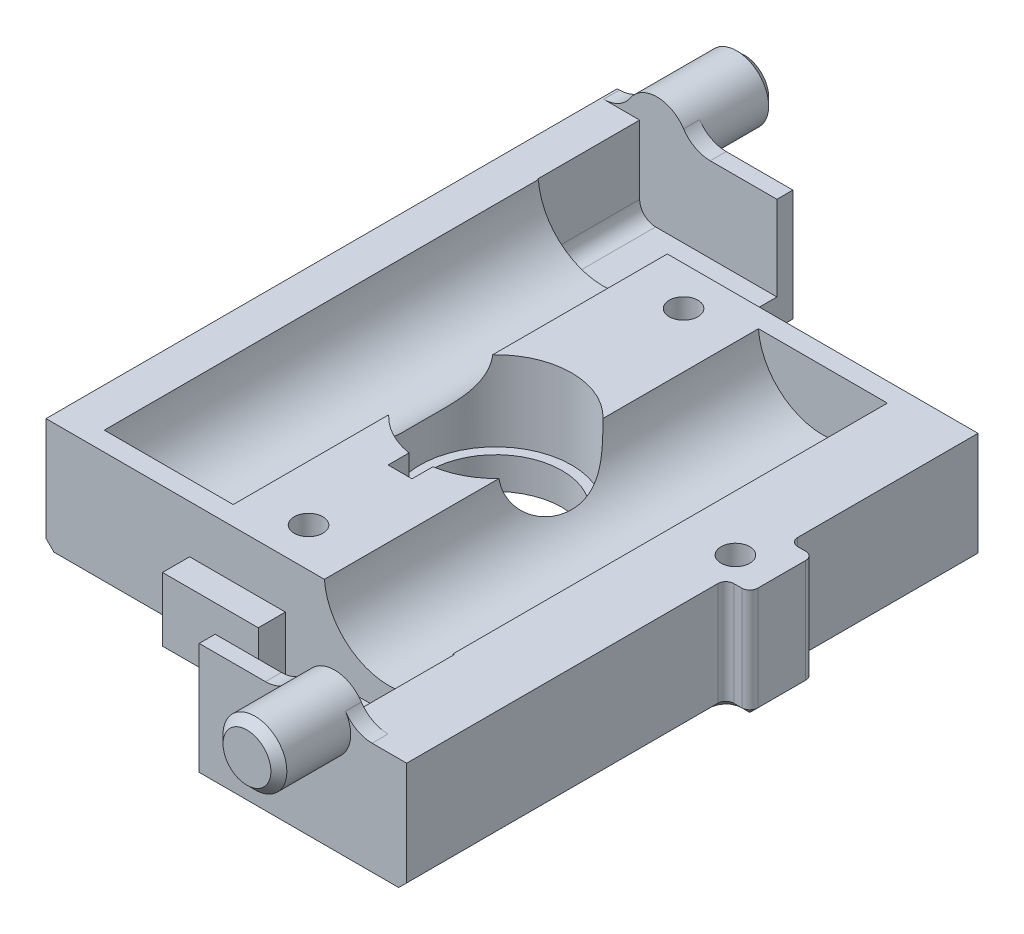
SolidWorks part; units mm, degrees
ref_plane "Front Plane" through (0, 0, 0) normal (0, 0, 1) x (1, 0, 0)
ref_plane "Top Plane" through (0, 0, 0) normal (0, 1, 0) x (1, 0, 0)
ref_plane "Right Plane" through (0, 0, 0) normal (1, 0, 0) x (0, 0, -1)
sketch "Sketch1" plane through (0, 0, 0) normal (0, 1, 0) x (1, 0, 0)
  line L1 (-61.4569, -66.3705) -> (-31.4569, -66.3705)
  line L2 (-61.4569, -66.3705) -> (-61.4569, -35.5705)
  line L3 (-61.4569, -35.5705) -> (-31.4569, -35.5705)
  line L4 (-31.4569, -66.3705) -> (-31.4569, -35.5705)
  dimension "D1" = 30.8
  dimension "D2" = 30
extrude "Boss-Extrude1" add sketch "Sketch1" along normal blind 7
sketch "Sketch2" plane through (0, 0, 0) normal (0, -1, 0) x (1, 0, 0)
  circle A0 centre (-47.4719, 50.9705) radius 4.15
  dimension "D1" = 8.3
extrude "Cut-Extrude1" cut sketch "Sketch2" against normal blind 6.5
sketch "Sketch3" plane through (0, 0, 0) normal (0, -1, 0) x (1, 0, 0)
  line L1 (-31.4569, 66.3705) -> (-46.4569, 66.3705)
  line L2 (-31.4569, 66.3705) -> (-31.4569, 65.1705)
  line L3 (-31.4569, 65.1705) -> (-46.4569, 65.1705)
  line L4 (-46.4569, 66.3705) -> (-46.4569, 65.1705)
  line L5 (-61.4569, 66.3705) -> (-52.4569, 66.3705)
  line L6 (-61.4569, 66.3705) -> (-61.4569, 65.1705)
  line L7 (-61.4569, 65.1705) -> (-52.4569, 65.1705)
  line L8 (-52.4569, 66.3705) -> (-52.4569, 65.1705)
  line L9 (-31.4569, 35.5705) -> (-42.4569, 35.5705)
  line L10 (-31.4569, 35.5705) -> (-31.4569, 36.7705)
  line L11 (-31.4569, 36.7705) -> (-42.4569, 36.7705)
  line L12 (-42.4569, 35.5705) -> (-42.4569, 36.7705)
  line L13 (-61.4569, 35.5705) -> (-48.4569, 35.5705)
  line L14 (-61.4569, 35.5705) -> (-61.4569, 36.7705)
  line L15 (-61.4569, 36.7705) -> (-48.4569, 36.7705)
  line L16 (-48.4569, 35.5705) -> (-48.4569, 36.7705)
  dimension "D1" = 15
  dimension "D2" = 9
  dimension "D3" = 1.2
  dimension "D4" = 1.2
  dimension "D5" = 1.2
  dimension "D6" = 1.2
  dimension "D7" = 11
  dimension "D8" = 13
extrude "Cut-Extrude2" cut sketch "Sketch3" against normal blind 4
sketch "Sketch4" plane through (0, 0, 66.3705) normal (0, 0, 1) x (1, 0, 0)
  line L1 (-61.4569, 7) -> (-31.4569, 7)
  line L2 (-61.4569, 7) -> (-61.4569, 4)
  line L3 (-61.4569, 4) -> (-31.4569, 4)
  line L4 (-31.4569, 7) -> (-31.4569, 4)
extrude "Cut-Extrude3" cut sketch "Sketch4" against normal blind 1.2
sketch "Sketch5" plane through (0, 0, 35.5705) normal (0, 0, -1) x (-1, 0, 0)
  line L1 (61.4569, 4) -> (31.4569, 4)
  line L2 (61.4569, 4) -> (61.4569, 7)
  line L3 (61.4569, 7) -> (31.4569, 7)
  line L4 (31.4569, 4) -> (31.4569, 7)
extrude "Cut-Extrude4" cut sketch "Sketch5" against normal blind 1.2
sketch "Sketch6" plane through (0, 0, 65.1705) normal (0, 0, 1) x (1, 0, 0)
  line L0 (-44.0746, 7.3) -> (-35.8746, 7.3) construction
  circle A0 centre (-39.9746, 7.3) radius 4.05
  dimension "D1" = 8.1
extrude "Cut-Extrude5" cut sketch "Sketch6" against normal blind 27.2
sketch "Sketch7" plane through (0, 0, 36.7705) normal (0, 0, -1) x (-1, 0, 0)
  line L0 (50.8646, 7.3) -> (59.0646, 7.3) construction
  circle A0 centre (54.9646, 7.3) radius 4.05
  dimension "D1" = 8.1
extrude "Cut-Extrude6" cut sketch "Sketch7" against normal blind 27.2
sketch "Sketch8" plane through (0, 7, 0) normal (0, 1, 0) x (1, 0, 0)
  circle A0 centre (-47.4719, -50.9705) radius 4.75
  dimension "D1" = 9.5
extrude "Cut-Extrude7" cut sketch "Sketch8" against normal blind 5
sketch "Sketch10" plane through (0, 0, 65.1705) normal (0, 0, 1) x (1, 0, 0)
  line L5 (-31.4569, 0) -> (-31.4569, 7)
  line L6 (-31.4569, 7) -> (-35.8569, 7)
  line L7 (-31.4569, 7) -> (-35.9357, 7) construction
  line L8 (-35.8569, 7) -> (-35.8569, 1.7)
  line L9 (-35.8569, 1.7) -> (-44.4569, 1.7)
  line L10 (-44.4569, 1.7) -> (-44.4569, 0)
  line L11 (-46.4569, 0) -> (-31.4569, 0) construction
  line L12 (-44.4569, 0) -> (-31.4569, 0)
  dimension "D1" = 4.4
  dimension "D2" = 1.7
  dimension "D3" = 13
extrude "Boss-Extrude2" add sketch "Sketch10" along normal blind 6.4
fillet "Fillet1" radius 1 1 edges at (-35.8569, 1.7, 68.3705)
sketch "Sketch11" plane through (0, 0, 36.7705) normal (0, 0, -1) x (-1, 0, 0)
  line L0 (61.4569, 7) -> (61.4569, 0)
  line L1 (61.4569, 0) -> (50.4569, 0)
  line L2 (48.4569, 0) -> (61.4569, 0) construction
  line L3 (50.4569, 0) -> (50.4569, 1.7)
  line L4 (50.4569, 1.7) -> (59.0569, 1.7)
  line L5 (59.0569, 1.7) -> (59.0569, 7)
  line L6 (61.4569, 7) -> (59.0034, 7) construction
  line L7 (59.0569, 7) -> (61.4569, 7)
  dimension "D1" = 2.4
  dimension "D2" = 1.7
  dimension "D3" = 11
extrude "Boss-Extrude3" add sketch "Sketch11" along normal blind 6.4
fillet "Fillet2" radius 1 1 edges at (-59.0569, 1.7, 33.5705)
sketch "Sketch12" plane through (0, 7, 0) normal (0, 1, 0) x (1, 0, 0)
  line L1 (-46.7219, -56.9705) -> (-48.2219, -56.9705)
  line L2 (-46.7219, -56.9705) -> (-46.7219, -55.6264)
  line L3 (-46.7219, -55.6264) -> (-48.2219, -55.6264)
  line L4 (-48.2219, -56.9705) -> (-48.2219, -55.6264)
  arc A0 (-46.9719, -55.5935) -> (-47.9719, -55.5935) centre (-47.4719, -50.9705) ccw construction
  dimension "D1" = 1.5
  dimension "D2" = 0.75
  dimension "D3" = 6
extrude "Cut-Extrude8" cut sketch "Sketch12" against normal up to surface (5 mm away) up to face at (-47.4719, 2, 55.7205)
sketch "Sketch13" plane through (0, 0, 71.5705) normal (0, 0, 1) x (1, 0, 0)
  line L0 (-44.0134, 7) -> (-61.4569, 7) construction
  line L1 (-31.4569, 0) -> (-44.4569, 0)
  line L2 (-31.4569, 0) -> (-31.4569, 7)
  line L3 (-31.4569, 7) -> (-44.4569, 7)
  line L4 (-44.4569, 0) -> (-44.4569, 7)
extrude "Boss-Extrude4" add sketch "Sketch13" along normal blind 1
sketch "Sketch14" plane through (0, 0, 30.3705) normal (0, 0, -1) x (-1, 0, 0)
  line L0 (50.9257, 7) -> (31.4569, 7) construction
  line L1 (61.4569, 0) -> (50.4569, 0)
  line L2 (61.4569, 0) -> (61.4569, 7)
  line L3 (61.4569, 7) -> (50.4569, 7)
  line L4 (50.4569, 0) -> (50.4569, 7)
extrude "Boss-Extrude5" add sketch "Sketch14" along normal blind 1
sketch "Sketch15" plane through (0, 0, 71.5705) normal (0, 0, 1) x (1, 0, 0)
  circle A0 centre (-36.9646, 6.8) radius 2
  dimension "D1" = 4
sketch "Sketch16" plane through (0, 0, 30.3705) normal (0, 0, -1) x (-1, 0, 0)
  circle A0 centre (57.9746, 6.8) radius 2
  dimension "D1" = 4
extrude "Boss-Extrude8" add sketch "Sketch15" along normal blind 5.5
extrude "Boss-Extrude9" add sketch "Sketch16" along normal blind 5.5
fillet "Fillet3" radius 2 1 edges at (-59.9645, 7, 29.8705)
fillet "Fillet4" radius 2 1 edges at (-55.9846, 7, 29.8705)
fillet "Fillet5" radius 2 2 edges at (-34.9746, 7, 72.0705) (-38.9545, 7, 72.0705)
chamfer "Chamfer2" distance 0.5 angle 45 1 edges at (-34.9646, 6.8, 77.0705)
chamfer "Chamfer3" distance 0.5 angle 45 1 edges at (-59.9746, 6.8, 24.8705)
sketch "Sketch17" plane through (-31.4569, 0, 0) normal (1, 0, 0) x (0, 0, -1)
  line L0 (-72.5705, 7) -> (-36.7705, 7) construction
  line L1 (-52.5705, 7) -> (-48.5705, 7)
  line L2 (-52.5705, 7) -> (-52.5705, 0)
  line L3 (-52.5705, 0) -> (-48.5705, 0)
  line L4 (-48.5705, 7) -> (-48.5705, 0)
  line L5 (-72.5705, 0) -> (-36.7705, 0) construction
  line L6 (-36.7705, 7) -> (-36.7705, 0) construction
  dimension "D1" = 4
  dimension "D2" = 11.8
extrude "Boss-Extrude10" add sketch "Sketch17" along normal blind 1.5
fillet "Fillet7" radius 0.5 4 edges at (-31.4569, 3.5, 52.5705) (-29.9569, 3.5, 52.5705) (-29.9569, 3.5, 48.5705) (-31.4569, 3.5, 48.5705)
sketch "Sketch18" plane through (0, 0, 0) normal (0, -1, 0) x (1, 0, 0)
  circle A0 centre (-32.4569, 50.9705) radius 0.9
  dimension "D1" = 1.8
extrude "Cut-Extrude9" cut sketch "Sketch18" against normal through all
sketch "Sketch19" plane through (0, 0, 0) normal (0, -1, 0) x (1, 0, 0)
  circle A0 centre (-32.4569, 50.9705) radius 1.6
  dimension "D1" = 3.2
extrude "Cut-Extrude10" cut sketch "Sketch19" against normal blind 2
sketch "Sketch20" plane through (0, 0, 0) normal (0, -1, 0) x (1, 0, 0)
  circle A0 centre (-47.4569, 62.7205) radius 0.9
  circle A1 centre (-47.4569, 39.2205) radius 0.9
  dimension "D1" = 1.8
  dimension "D2" = 1.8
extrude "Cut-Extrude11" cut sketch "Sketch20" against normal through all
sketch "Sketch21" plane through (0, 0, 0) normal (0, -1, 0) x (1, 0, 0)
  circle A0 centre (-47.4569, 62.7205) radius 1.6
  circle A1 centre (-47.4569, 39.2205) radius 1.6
  dimension "D1" = 3.2
  dimension "D2" = 3.2
extrude "Cut-Extrude12" cut sketch "Sketch21" against normal blind 2
chamfer "Chamfer6" distance 0.5 angle 45 9 edges at (-61.4569, 0, 47.2705) (-31.3104, 0, 48.4241) (-30.7069, 0, 48.5705) (-30.1033, 0, 48.717) (-29.9569, 0, 50.5705) (-30.1033, 0, 52.4241) (-30.7069, 0, 52.5705) (-31.3104, 0, 52.717) (-31.4569, 0, 62.8205)
sketch "Sketch22" plane through (0, 0, 35.5705) normal (0, 0, -1) x (-1, 0, 0)
  line L1 (42.4569, 4) -> (48.4569, 4)
  line L2 (42.4569, 4) -> (42.4569, 0)
  line L3 (42.4569, 0) -> (48.4569, 0)
  line L4 (48.4569, 4) -> (48.4569, 0)
extrude "Boss-Extrude11" add sketch "Sketch22" along normal blind 0.5
sketch "Sketch23" plane through (0, 0, 66.3705) normal (0, 0, 1) x (1, 0, 0)
  line L1 (-52.4569, 4) -> (-46.4569, 4)
  line L2 (-52.4569, 4) -> (-52.4569, 0)
  line L3 (-52.4569, 0) -> (-46.4569, 0)
  line L4 (-46.4569, 4) -> (-46.4569, 0)
extrude "Boss-Extrude12" add sketch "Sketch23" along normal blind 0.5
